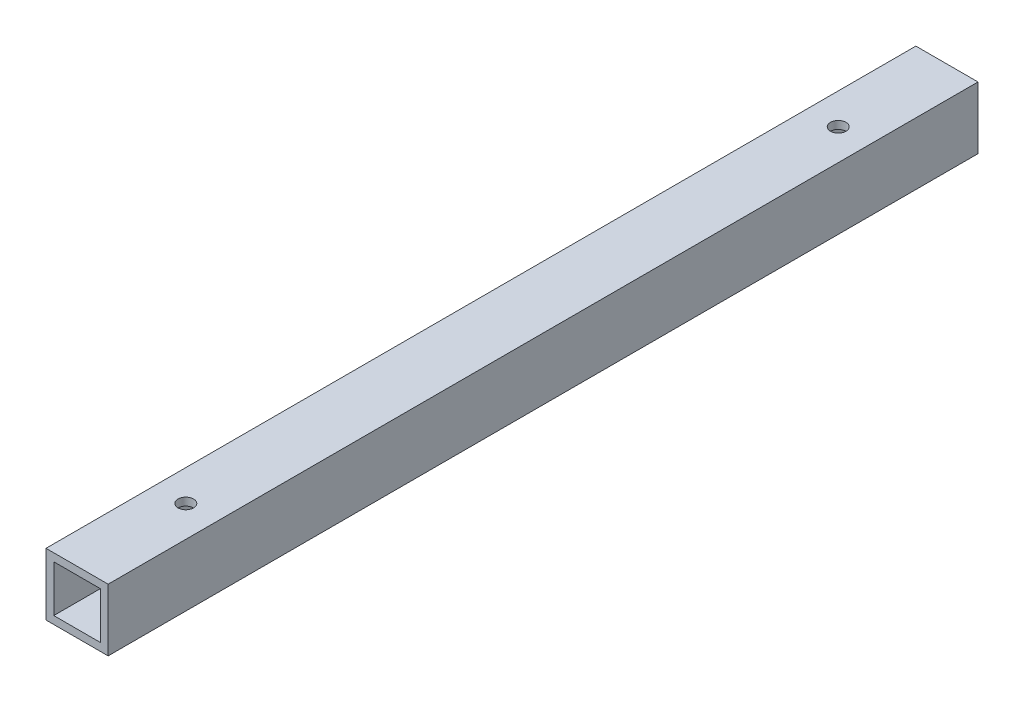
SolidWorks part; units mm, degrees
material "6061 Alloy"
ref_plane "Front Plane" through (0, 0, 0) normal (0, 0, 1) x (1, 0, 0)
ref_plane "Top Plane" through (0, 0, 0) normal (0, 1, 0) x (1, 0, 0)
ref_plane "Right Plane" through (0, 0, 0) normal (1, 0, 0) x (0, 0, -1)
sketch "Sketch1" plane through (0, 0, 0) normal (0, 0, 1) x (1, 0, 0)
  line L0 (12.7, 0) -> (9.525, 0) construction
  line L1 (-12.7, 0) -> (12.7, 0) construction
  line L2 (0, 12.7) -> (0, -12.7)
  point P7 (0, 0)
sketch "Sketch2" plane through (0, 0, 0) normal (1, 0, 0) x (0, 0, -1)
  line L0 (177.8, 0) -> (-177.8, 0)
  point P4 (0, 0)
  dimension "Length" = 355.6
sketch "Sketch3" plane through (0, 0, 0) normal (0, 0, 1) x (1, 0, 0)
  line L0 (-12.7, 0) -> (12.7, 0) construction
  line L5 (12.7, -12.7) -> (-12.7, -12.7)
  line L6 (12.7, -12.7) -> (12.7, 12.7)
  line L11 (12.7, 12.7) -> (-12.7, 12.7)
  line L12 (-12.7, -12.7) -> (-12.7, 12.7)
  line L14 (12.7, -12.7) -> (-12.7, 12.7) construction
  line L15 (12.7, 12.7) -> (-12.7, -12.7) construction
  line L16 (9.525, -9.525) -> (-9.525, -9.525)
  line L17 (9.525, -9.525) -> (9.525, 9.525)
  line L18 (9.525, 9.525) -> (-9.525, 9.525)
  line L19 (-9.525, -9.525) -> (-9.525, 9.525)
  line L20 (9.525, -9.525) -> (-9.525, 9.525) construction
  line L21 (9.525, 9.525) -> (-9.525, -9.525) construction
  point P0 (0, 0)
  point P5 (0, 0)
  point P13 (9.525, -12.7)
  dimension "D1" = 3.175
  dimension "D3" = 25.4
  dimension "D4" = 25.4
extrude "Boss-Extrude1" add sketch "Sketch3" along normal up to vertex (177.8 mm away) and the other way up to vertex (177.8 mm away) up to point (0, 0, 177.8) other way up to point (0, 0, -177.8)
sketch "Sketch5" plane through (0, 0, 0) normal (1, 0, 0) x (0, 0, -1)
  line L0 (-177.8, 0) -> (177.8, 0) construction
  line L3 (-177.8, -12.7) -> (-177.8, 12.7) construction
  line L4 (177.8, -12.7) -> (177.8, 12.7) construction
  point P6 (-149.225, 0)
  point P7 (-139.7, 0)
  point P8 (139.7, 0)
  point P10 (149.225, 0)
  dimension "D1" = 28.575
  dimension "D2" = 38.1
  dimension "D3" = 28.575
  dimension "D4" = 38.1
sketch "Sketch7" plane through (0, 12.7, 0) normal (0, 1, 0) x (1, 0, 0)
  line L0 (0, -177.8) -> (0, 177.8) construction
  line L1 (12.7, -177.8) -> (-12.7, -177.8) construction
  line L2 (12.7, 177.8) -> (-12.7, 177.8) construction
  line L3 (-12.7, 0) -> (12.7, 0) construction
  line L4 (-12.7, -177.8) -> (-12.7, 177.8) construction
  line L5 (12.7, -177.8) -> (12.7, 177.8) construction
  circle A0 centre (0, -133.35) radius 3.175
  circle A1 centre (0, 133.35) radius 3.175
  dimension "D1" = 6.35
  dimension "D2" = 44.45
extrude "Cut-Extrude2" cut sketch "Sketch7" against normal through all both and the other way through all
equation "\"D1@Sketch3\"=\"Wall thickness@Sketch1\""
equation "\"D1@Sketch5\"=\"Width@Sketch1\"*1.125"
equation "\"D2@Sketch5\"=\"Width@Sketch1\"*1.5"
equation "\"D3@Sketch5\"=\"D1@Sketch5\""
equation "\"D4@Sketch5\"=\"D2@Sketch5\""
equation "\"D2@Sketch3\"=\"Wall Thickness@Sketch1\""
